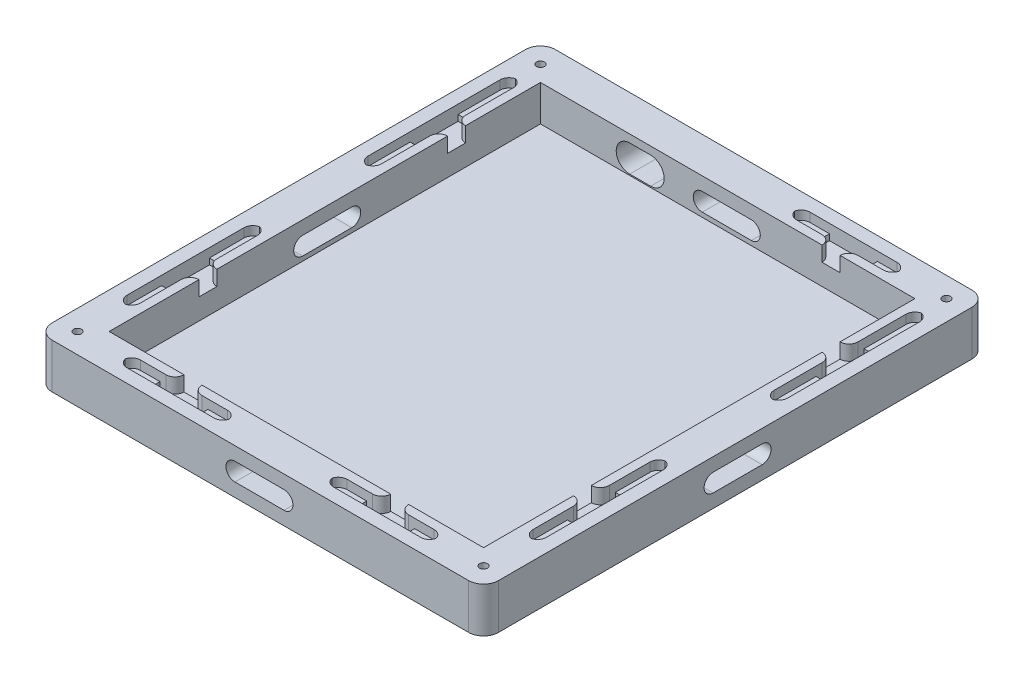
SolidWorks part; units mm, degrees
ref_plane "Front Plane" through (0, 0, 0) normal (0, 0, 1) x (1, 0, 0)
ref_plane "Top Plane" through (0, 0, 0) normal (0, 1, 0) x (1, 0, 0)
ref_plane "Right Plane" through (0, 0, 0) normal (1, 0, 0) x (0, 0, -1)
sketch "Sketch1" plane through (0, 0, 0) normal (0, 1, 0) x (1, 0, 0)
  line L0 (-62.5, 55.915) -> (-62.5, 72)
  line L1 (-47.54, -72) -> (46.365, -72)
  line L2 (-62.5, -57.04) -> (-62.5, 55.915)
  line L3 (-47.54, 72) -> (46.365, 72)
  line L4 (62.5, -57.04) -> (62.5, 55.915)
  line L5 (-62.5, -72) -> (62.5, 72) construction
  line L6 (-62.5, 72) -> (62.5, -72) construction
  line L7 (-62.5, 72) -> (-47.54, 72)
  line L9 (46.365, 72) -> (62.5, 72)
  line L10 (62.5, 72) -> (62.5, 55.915)
  line L12 (62.5, -57.04) -> (62.5, -72)
  line L13 (62.5, -72) -> (46.365, -72)
  line L15 (-47.54, -72) -> (-62.5, -72)
  line L16 (-62.5, -72) -> (-62.5, -57.04)
  line L17 (-74.5, 84) -> (74.5, 84)
  line L18 (74.5, 84) -> (74.5, -84)
  line L19 (74.5, -84) -> (-74.5, -84)
  line L20 (-74.5, -84) -> (-74.5, 84)
  point P0 (0, 0)
  dimension "D3" = 12
  dimension "D5" = 12
  dimension "D4" = 12
  dimension "D6" = 12
  dimension "D1" = 125
  dimension "D2" = 144
extrude "Floor" add sketch "Sketch1" along normal blind 3 contours L16 L2 L0 L7 L3 L9 L10 L4 L12 L13 L1 L15
sketch "Sketch4" plane through (0, 3, 0) normal (0, 1, 0) x (1, 0, 0)
  line L0 (-74.5, 84) -> (74.5, 84)
  line L1 (74.5, 84) -> (74.5, -84)
  line L2 (74.5, -84) -> (-74.5, -84)
  line L3 (-74.5, -84) -> (-74.5, 84)
  line L4 (-62.5, 72) -> (62.5, 72) construction
  line L5 (62.5, 72) -> (62.5, -72) construction
  line L6 (62.5, -72) -> (-62.5, -72) construction
  line L7 (-62.5, -72) -> (-62.5, 72) construction
  line L8 (-62.5, 72) -> (-62.5, -72)
  line L9 (-62.5, -72) -> (62.5, -72)
  line L10 (62.5, -72) -> (62.5, 72)
  line L11 (62.5, 72) -> (-62.5, 72)
  dimension "D1" = 12
  dimension "D2" = 12
  dimension "D3" = 12
  dimension "D4" = 12
extrude "Boss-Extrude1" add sketch "Sketch4" along normal blind 12 and the other way blind 3
fillet "Fillet1" radius 5 1 edges at (-74.5, 7.5, 84)
fillet "Fillet2" radius 5 1 edges at (74.5, 7.5, 84)
fillet "Fillet3" radius 5 1 edges at (74.5, 7.5, -84)
fillet "Fillet4" radius 5 1 edges at (-74.5, 7.5, -84)
sketch "Sketch5" plane through (0, 15, 0) normal (0, 1, 0) x (1, 0, 0)
  line L0 (-62.5, 47) -> (-62.5, 41)
  line L1 (-62.5, 41) -> (-65.5, 41)
  line L2 (-65.5, 41) -> (-65.5, 19)
  line L3 (-65.5, 19) -> (-70, 19)
  line L4 (-70, 19) -> (-70, 69)
  line L5 (-70, 69) -> (-65.5, 69)
  line L6 (-65.5, 69) -> (-65.5, 47)
  line L7 (-65.5, 47) -> (-62.5, 47)
  line L8 (-62.5, 72) -> (-62.5, 47) construction
  line L9 (-62.5, 72) -> (-62.5, -72) construction
  line L10 (-62.5, 72) -> (-62.5, 7) construction
  line L11 (-62.5, -36) -> (-62.5, -42)
  line L12 (-62.5, -42) -> (-65.5, -42)
  line L13 (-65.5, -42) -> (-65.5, -61.5)
  line L14 (-65.5, -61.5) -> (-70, -61.5)
  line L15 (-70, -61.5) -> (-70, -16.5)
  line L16 (-70, -16.5) -> (-65.5, -16.5)
  line L17 (-65.5, -16.5) -> (-65.5, -36)
  line L18 (-65.5, -36) -> (-62.5, -36)
  line L19 (-62.5, 7) -> (-62.5, -7) construction
  line L20 (-62.5, -72) -> (-62.5, -42) construction
  line L21 (-62.5, -72) -> (-62.5, 72) construction
  line L22 (62.5, -36) -> (62.5, -42)
  line L23 (62.5, -42) -> (65.5, -42)
  line L24 (65.5, -42) -> (65.5, -61.5)
  line L25 (65.5, -61.5) -> (70, -61.5)
  line L26 (70, -61.5) -> (70, -16.5)
  line L27 (70, -16.5) -> (65.5, -16.5)
  line L28 (65.5, -16.5) -> (65.5, -36)
  line L29 (65.5, -36) -> (62.5, -36)
  line L30 (62.5, -72) -> (62.5, -42) construction
  line L31 (62.5, -72) -> (62.5, 72) construction
  line L32 (62.5, 47) -> (62.5, 41)
  line L33 (62.5, 41) -> (65.5, 41)
  line L34 (65.5, 41) -> (65.5, 19)
  line L35 (65.5, 19) -> (70, 19)
  line L36 (70, 19) -> (70, 69)
  line L37 (70, 69) -> (65.5, 69)
  line L38 (65.5, 69) -> (65.5, 47)
  line L39 (65.5, 47) -> (62.5, 47)
  line L40 (62.5, 72) -> (62.5, 47) construction
  line L41 (62.5, 72) -> (7, 72) construction
  line L42 (62.5, 72) -> (37.5, 72) construction
  line L43 (62.5, 72) -> (-62.5, 72) construction
  line L54 (31.5, 72) -> (37.5, 72)
  line L55 (37.5, 72) -> (37.5, 75)
  line L56 (37.5, 75) -> (52, 75)
  line L57 (52, 75) -> (52, 79.5)
  line L58 (52, 79.5) -> (17, 79.5)
  line L59 (17, 79.5) -> (17, 75)
  line L60 (17, 75) -> (31.5, 75)
  line L61 (31.5, 75) -> (31.5, 72)
  line L62 (-37.5, -72) -> (-31.5, -72)
  line L63 (-31.5, -72) -> (-31.5, -75)
  line L64 (-31.5, -75) -> (-17, -75)
  line L65 (-17, -75) -> (-17, -79.5)
  line L66 (-17, -79.5) -> (-52, -79.5)
  line L67 (-52, -79.5) -> (-52, -75)
  line L68 (-52, -75) -> (-37.5, -75)
  line L69 (-37.5, -75) -> (-37.5, -72)
  line L70 (-62.5, -72) -> (-37.5, -72) construction
  line L71 (-62.5, -72) -> (62.5, -72) construction
  line L72 (31.5, -72) -> (37.5, -72)
  line L73 (37.5, -72) -> (37.5, -75)
  line L74 (37.5, -75) -> (52, -75)
  line L75 (52, -75) -> (52, -79.5)
  line L76 (52, -79.5) -> (17, -79.5)
  line L77 (17, -79.5) -> (17, -75)
  line L78 (17, -75) -> (31.5, -75)
  line L79 (31.5, -75) -> (31.5, -72)
  line L80 (62.5, -72) -> (37.5, -72) construction
  line L81 (62.5, -72) -> (-62.5, -72) construction
  dimension "D1" = 6
  dimension "D2" = 3
  dimension "D3" = 4.5
  dimension "D4" = 50
  dimension "D5" = 25
  dimension "D6" = 65
  dimension "D7" = 55.5
  dimension "D8" = 6
  dimension "D9" = 3
  dimension "D10" = 4.5
  dimension "D11" = 45
  dimension "D12" = 14
  dimension "D13" = 30
  dimension "D14" = 6
  dimension "D15" = 3
  dimension "D16" = 4.5
  dimension "D17" = 45
  dimension "D18" = 30
  dimension "D19" = 25
  dimension "D20" = 4.5
  dimension "D21" = 50
  dimension "D22" = 6
  dimension "D23" = 3
  dimension "D24" = 25
  dimension "D31" = 4.5
  dimension "D32" = 35
  dimension "D33" = 6
  dimension "D34" = 3
  dimension "D35" = 6
  dimension "D36" = 3
  dimension "D37" = 4.5
  dimension "D38" = 35
  dimension "D39" = 25
  dimension "D40" = 3
  dimension "D41" = 4.5
  dimension "D42" = 35
  dimension "D43" = 6
  dimension "D44" = 25
extrude "Cut-Extrude1" cut sketch "Sketch5" against normal blind 3
sketch "Sketch6" plane through (0, 12, 0) normal (0, 1, 0) x (1, 0, 0)
  line L51 (31.5, 72) -> (37.5, 72)
  line L53 (37.5, 72) -> (37.5, 75)
  line L109 (37.5, 75) -> (42.5, 75)
  line L110 (42.5, 75) -> (42.5, 79.5)
  line L111 (42.5, 79.5) -> (26.5, 79.5)
  line L112 (26.5, 79.5) -> (26.5, 75)
  line L113 (26.5, 75) -> (31.5, 75)
  line L114 (31.5, 75) -> (31.5, 72)
  line L115 (62.5, 47) -> (62.5, 41)
  line L116 (62.5, 41) -> (65.5, 41)
  line L117 (65.5, 41) -> (65.5, 36)
  line L118 (65.5, 36) -> (70, 36)
  line L119 (70, 36) -> (70, 52)
  line L120 (70, 52) -> (65.5, 52)
  line L121 (65.5, 52) -> (65.5, 47)
  line L122 (65.5, 47) -> (62.5, 47)
  line L131 (-62.5, 47) -> (-65.5, 47)
  line L132 (-65.5, 47) -> (-65.5, 52)
  line L133 (-65.5, 52) -> (-70, 52)
  line L134 (-70, 52) -> (-70, 36)
  line L135 (-70, 36) -> (-65.5, 36)
  line L136 (-65.5, 36) -> (-65.5, 41)
  line L137 (-65.5, 41) -> (-62.5, 41)
  line L138 (-62.5, 41) -> (-62.5, 47)
  line L139 (-62.5, -36) -> (-65.5, -36)
  line L140 (-65.5, -36) -> (-65.5, -31)
  line L141 (-65.5, -31) -> (-70, -31)
  line L142 (-70, -31) -> (-70, -47)
  line L143 (-70, -47) -> (-65.5, -47)
  line L144 (-65.5, -47) -> (-65.5, -42)
  line L145 (-65.5, -42) -> (-62.5, -42)
  line L146 (-62.5, -42) -> (-62.5, -36)
  line L147 (-37.5, -72) -> (-37.5, -75)
  line L148 (-37.5, -75) -> (-42.5, -75)
  line L149 (-42.5, -75) -> (-42.5, -79.5)
  line L150 (-42.5, -79.5) -> (-26.5, -79.5)
  line L151 (-26.5, -79.5) -> (-26.5, -75)
  line L152 (-26.5, -75) -> (-31.5, -75)
  line L153 (-31.5, -75) -> (-31.5, -72)
  line L154 (-31.5, -72) -> (-37.5, -72)
  line L155 (31.5, -72) -> (31.5, -75)
  line L156 (31.5, -75) -> (26.5, -75)
  line L157 (26.5, -75) -> (26.5, -79.5)
  line L158 (26.5, -79.5) -> (42.5, -79.5)
  line L159 (42.5, -79.5) -> (42.5, -75)
  line L160 (42.5, -75) -> (37.5, -75)
  line L161 (37.5, -75) -> (37.5, -72)
  line L162 (37.5, -72) -> (31.5, -72)
  line L163 (62.5, -36) -> (62.5, -42)
  line L164 (62.5, -42) -> (65.5, -42)
  line L165 (65.5, -42) -> (65.5, -47)
  line L166 (65.5, -47) -> (70, -47)
  line L167 (70, -47) -> (70, -31)
  line L168 (70, -31) -> (65.5, -31)
  line L169 (65.5, -31) -> (65.5, -36)
  line L170 (65.5, -36) -> (62.5, -36)
extrude "Cut-Extrude2" cut sketch "Sketch6" against normal blind 2
sketch "Sketch7" plane through (-74.5, 0, 0) normal (-1, 0, 0) x (0, 0, 1)
  line L0 (-84, 7.5) -> (-12, 7.5) construction
  line L1 (-84, 0) -> (-84, 15) construction
  line L2 (-9, 10.5) -> (7.38, 10.5)
  line L3 (-9, 4.5) -> (7.38, 4.5)
  line L4 (-12, 4.845) -> (-12, 10.155) construction
  arc A0 (-9, 4.5) -> (-9, 10.5) centre (-9, 7.5) cw
  arc A1 (7.38, 10.5) -> (7.38, 4.5) centre (7.38, 7.5) cw
  point P10 (-9, 10.5)
  point P13 (-12, 7.5)
  dimension "D3" = 3
  dimension "D1" = 72
  dimension "D2" = 16.38
extrude "Cut-Extrude3" cut sketch "Sketch7" against normal through all
sketch "Sketch8" plane through (0, 0, 84) normal (0, 0, 1) x (1, 0, 0)
  line L0 (-74.5, 7.5) -> (-11.5, 7.5) construction
  line L1 (-74.5, 0) -> (-74.5, 15) construction
  line L2 (-8.5, 10.5) -> (7.88, 10.5)
  line L3 (-8.5, 4.5) -> (7.88, 4.5)
  line L4 (-11.5, 4.845) -> (-11.5, 10.155) construction
  arc A0 (-8.5, 4.5) -> (-8.5, 10.5) centre (-8.5, 7.5) cw
  arc A1 (7.88, 10.5) -> (7.88, 4.5) centre (7.88, 7.5) cw
  point P10 (-8.5, 10.5)
  point P13 (-11.5, 7.5)
  dimension "D3" = 3
  dimension "D1" = 63
  dimension "D2" = 16.38
extrude "Cut-Extrude4" cut sketch "Sketch8" against normal through all
sketch "Sketch9" plane through (0, 0, 0) normal (0, -1, 0) x (1, 0, 0)
  circle A0 centre (-67.7678, 77.2678) radius 1.325
  circle A1 centre (67.7678, 77.2678) radius 1.325
  circle A2 centre (67.7678, -77.2678) radius 1.325
  circle A3 centre (-67.7678, -77.2678) radius 1.325
  dimension "D1" = 2.65
  dimension "D2" = 2.65
  dimension "D3" = 2.65
  dimension "D4" = 2.65
extrude "Cut-Extrude5" cut sketch "Sketch9" against normal blind 17
sketch "Sketch10" plane through (0, 0, 0) normal (0, -1, 0) x (1, 0, 0)
  circle A0 centre (-67.7678, 77.2678) radius 3
  circle A1 centre (67.7678, 77.2678) radius 3
  circle A2 centre (67.7678, -77.2678) radius 3
  circle A3 centre (-67.7678, -77.2678) radius 3
  dimension "D1" = 6
  dimension "D2" = 6
  dimension "D3" = 6
  dimension "D4" = 6
extrude "Cut-Extrude6" cut sketch "Sketch10" against normal blind 5
sketch "Sketch11" plane through (0, 0, 0) normal (0, -1, 0) x (1, 0, 0)
  line L0 (-62.5, 72) -> (-62.5, -72) construction
  line L1 (62.5, 72) -> (-62.5, 72) construction
  line L2 (62.5, -72) -> (62.5, 72) construction
  line L3 (-62.5, -72) -> (62.5, -72) construction
  circle A0 centre (-42.5, 52) radius 6.25
  circle A1 centre (42.5, 52) radius 6.25
  circle A2 centre (-42.5, -52) radius 6.25
  circle A3 centre (42.5, -52) radius 6.25
  dimension "D1" = 12.5
  dimension "D2" = 12.5
  dimension "D3" = 12.5
  dimension "D4" = 12.5
  dimension "D5" = 20
  dimension "D6" = 20
  dimension "D7" = 20
  dimension "D8" = 20
  dimension "D9" = 20
  dimension "D10" = 20
  dimension "D11" = 20
  dimension "D12" = 20
extrude "Cut-Extrude7" cut sketch "Sketch11" against normal blind 1
sketch "Sketch12" plane through (0, 0, -84) normal (0, 0, -1) x (-1, 0, 0)
  line L0 (-69.5, 15) -> (69.5, 15) construction
  line L2 (32.713, 7.9) -> (25.713, 7.9) construction
  line L3 (32.713, 3.4) -> (25.713, 3.4)
  line L4 (32.713, 12.4) -> (25.713, 12.4)
  line L5 (74.5, 15) -> (74.5, 0) construction
  arc A0 (32.713, 3.4) -> (32.713, 12.4) centre (32.713, 7.9) ccw
  arc A1 (25.713, 12.4) -> (25.713, 3.4) centre (25.713, 7.9) ccw
  point P6 (29.213, 7.9)
  dimension "D1" = 7.1
  dimension "D2" = 7
  dimension "D3" = 9
  dimension "D4" = 45.287
extrude "Cut-Extrude8" cut sketch "Sketch12" against normal blind 20
fillet "Fillet5" radius 3 4 edges at (17, 13.5, -75) (17, 13.5, -79.5) (52, 13.5, -75) (52, 13.5, -79.5)
fillet "Fillet6" radius 3 2 edges at (37.5, 12.5, -75) (31.5, 12.5, -75)
fillet "Fillet7" radius 3 6 edges at (65.5, 12.5, -41) (65.5, 13.5, -19) (70, 13.5, -19) (70, 13.5, -69) (65.5, 13.5, -69) (65.5, 12.5, -47)
fillet "Fillet8" radius 3 6 edges at (65.5, 12.5, 42) (65.5, 13.5, 61.5) (70, 13.5, 61.5) (65.5, 13.5, 16.5) (70, 13.5, 16.5) (65.5, 12.5, 36)
fillet "Fillet9" radius 3 6 edges at (31.5, 12.5, 75) (17, 13.5, 75) (17, 13.5, 79.5) (37.5, 12.5, 75) (52, 13.5, 79.5) (52, 13.5, 75)
fillet "Fillet10" radius 3 6 edges at (-37.5, 12.5, 75) (-52, 13.5, 75) (-52, 13.5, 79.5) (-17, 13.5, 79.5) (-17, 13.5, 75) (-31.5, 12.5, 75)
fillet "Fillet11" radius 3 6 edges at (-65.5, 12.5, 36) (-65.5, 13.5, 16.5) (-70, 13.5, 16.5) (-70, 13.5, 61.5) (-65.5, 13.5, 61.5) (-65.5, 12.5, 42)
fillet "Fillet12" radius 3 6 edges at (-65.5, 12.5, -47) (-65.5, 13.5, -69) (-70, 13.5, -69) (-70, 13.5, -19) (-65.5, 13.5, -19) (-65.5, 12.5, -41)
